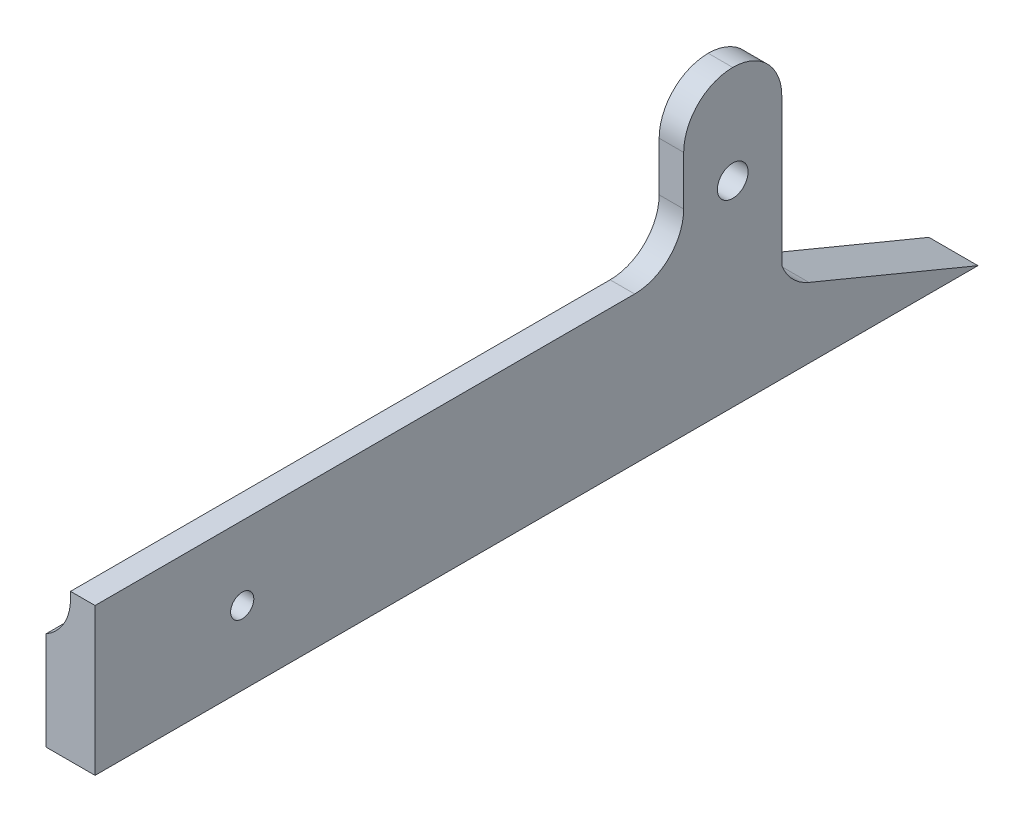
SolidWorks part; units mm, degrees
ref_plane "Front Plane" through (0, 0, 0) normal (0, 0, 1) x (1, 0, 0)
ref_plane "Top Plane" through (0, 0, 0) normal (0, 1, 0) x (1, 0, 0)
ref_plane "Right Plane" through (0, 0, 0) normal (1, 0, 0) x (0, 0, -1)
sketch "Sketch1" plane through (0, 0, 0) normal (1, 0, 0) x (0, 0, -1)
  line L1 (0, 14.692) -> (50.8, -6.35)
  line L2 (50.8, -6.35) -> (-25.4, -6.35)
  line L3 (-25.4, -6.35) -> (-25.4, 6.35)
  line L4 (-25.4, 6.35) -> (-25.4, 19.05)
  line L5 (-25.4, 19.05) -> (0, 19.05)
  line L6 (0, 19.05) -> (0, 14.692)
  dimension "D1" = 76.2
  dimension "D2" = 25.4
  dimension "D3" = 12.7
  dimension "D4" = 6.35
  dimension "D5" = 25.4
  dimension "D6" = 25.4
  dimension "D7" = 22.5
extrude "Boss-Extrude1" add sketch "Sketch1" along normal blind 6.35
fillet "Fillet1" radius 12.7 1 edges at (3.175, 14.692, 0)
sketch "Sketch2" plane through (6.35, 0, 0) normal (1, 0, 0) x (0, 0, -1)
  line L0 (-25.4, -6.35) -> (50.8, -6.35) construction
  line L2 (0, 19.05) -> (0, 69.85)
  line L3 (0, 69.85) -> (-25.4, 69.85)
  line L4 (-25.4, -6.35) -> (-25.4, 69.85)
  line L5 (-25.4, 19.05) -> (-25.4, -6.35) construction
  line L6 (50.8, -6.35) -> (7.0297, 11.7802) construction
  line L7 (-25.4, -6.35) -> (50.8, -6.35)
  line L8 (50.8, -6.35) -> (7.0297, 11.7802)
  arc A0 (0, 19.05) -> (7.0297, 11.7802) centre (11.8898, 23.5135) ccw construction
  arc A1 (0, 19.05) -> (7.0297, 11.7802) centre (11.8898, 23.5135) ccw
  dimension "D1" = 76.2
extrude "Boss-Extrude2" add sketch "Sketch2" along normal blind 6.35
fillet "Fillet2" radius 12.7 1 edges at (6.35, 19.05, 12.7)
sketch "Sketch3" plane through (12.7, 0, 0) normal (1, 0, 0) x (0, 0, -1)
  line L0 (0, 69.85) -> (-25.4, 69.85) construction
  line L1 (-25.4, -6.35) -> (50.8, -6.35) construction
  circle A0 centre (-12.7, 44.45) radius 3.9688
  point P5 (-12.7, 69.85)
  dimension "D1" = 7.9375
  dimension "D2" = 50.8
extrude "Cut-Extrude1" cut sketch "Sketch3" against normal through all both
fillet "Fillet3" radius 12.7 2 edges at (9.525, 69.85, 0) (9.525, 69.85, 25.4)
sketch "Sketch4" plane through (0, 0, 25.4) normal (0, 0, 1) x (1, 0, 0)
  line L6 (6.35, 30.0485) -> (6.35, 31.75)
  line L7 (6.35, 57.15) -> (6.35, 30.0485) construction
  line L8 (6.35, 31.75) -> (12.7, 31.75)
  line L9 (12.7, 57.15) -> (12.7, -6.35) construction
  line L10 (12.7, -6.35) -> (12.7, 57.15)
  line L11 (12.7, 57.15) -> (6.35, 57.15)
  line L12 (6.35, 57.15) -> (6.35, 30.0485)
  line L13 (0, 19.05) -> (0, -6.35)
  line L14 (0, -6.35) -> (12.7, -6.35)
  line L18 (0, 19.05) -> (0, -6.35)
  line L19 (0, -6.35) -> (12.7, -6.35)
  line L20 (12.7, 31.75) -> (12.7, -6.35)
  arc A2 (0, 19.05) -> (6.35, 30.0485) centre (-6.35, 30.0485) ccw
  arc A3 (0, 19.05) -> (6.35, 30.0485) centre (-6.35, 30.0485) ccw
  dimension "D2" = 38.1
  dimension "D1" = 0
extrude "Boss-Extrude3" add sketch "Sketch4" along normal blind 152.4
fillet "Fillet4" radius 12.7 1 edges at (9.525, 31.75, 25.4)
sketch "Sketch5" plane through (0, 0, 0) normal (-1, 0, 0) x (0, 0, 1)
  line L0 (177.8, -6.35) -> (-50.8, -6.35) construction
  line L1 (177.8, 19.05) -> (177.8, -6.35) construction
  circle A0 centre (139.7, 12.7) radius 3
  dimension "D3" = 6
  dimension "D1" = 19.05
  dimension "D2" = 38.1
extrude "Cut-Extrude2" cut sketch "Sketch5" against normal through all both
